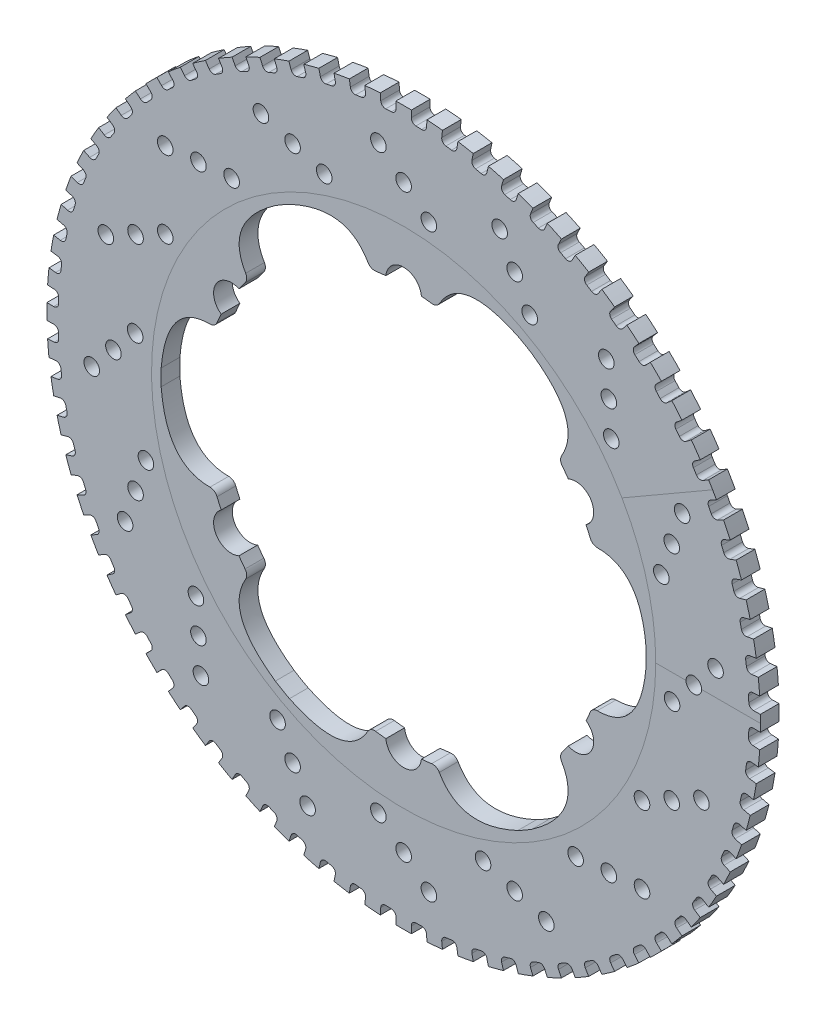
SolidWorks part; units mm, degrees
material "1023 Carbon Steel Sheet (SS)"
ref_plane "Front Plane" through (0, 0, 0) normal (0, 0, 1) x (1, 0, 0)
ref_plane "Top Plane" through (0, 0, 0) normal (0, 1, 0) x (1, 0, 0)
ref_plane "Right Plane" through (0, 0, 0) normal (1, 0, 0) x (0, 0, -1)
sketch "Sketch2" plane through (0, 0, 0) normal (0, 0, 1) x (1, 0, 0)
  circle A0 centre (0, 0) radius 95.25
  circle A1 centre (0, 0) radius 64.77
  circle A2 centre (0, 0) radius 53.086 construction
  dimension "D1" = 190.5
  dimension "D2" = 30.48
  dimension "D3" = 106.172
extrude "RotorSwept" add sketch "Sketch2" along normal blind 5
sketch "Sketch3" plane through (0, 0, 5) normal (0, 0, 1) x (1, 0, 0)
  line L0 (0, 53.086) -> (0, 64.77) construction
  circle A0 centre (0, 0) radius 53.086 construction
  circle A1 centre (0, 53.086) radius 4.7625
  circle A2 centre (0, 0) radius 53.721
  circle A3 centre (0, 0) radius 64.77 construction
  spline S0 degree 2 poles (-8.89, 52.9803) (-14.4253, 64.6738) (-30.48, 57.15) knots 0 0 0 1 1 1
  spline S1 degree 2 poles (8.89, 52.9803) (14.4253, 64.6738) (30.48, 57.15) knots 0 0 0 1 1 1
  circle M3 centre (0, 0) radius 64.77
  dimension "D1" = 106.172
  dimension "D2" = 9.525
  dimension "D5" = 11.43
  dimension "D4" = 8.89
  dimension "D6" = 30.48
  dimension "D7" = 3.81
  dimension "D3" = 0.635
extrude "FloatPinIF" add sketch "Sketch3" along direction (0, 0, 1) on the side against the normal through all contours A2 S1 S0 A1 M3 region at (0, 59.9234, 5)
pattern_circular "FloatPinPattern" count 6 over 360 about axis through (0, 0, 5) along (0, 0, -1) of "FloatPinIF" reverse direction yes
sketch "Sketch4" plane through (0, 0, 5) normal (0, 0, 1) x (1, 0, 0)
  line L0 (-6.7401, 83.2668) -> (6.7401, 71.6732) construction
  line L1 (0, 0) -> (-6.7401, 83.2668) construction
  line L2 (6.7401, 71.6732) -> (0, 0) construction
  circle A0 centre (0, 0) radius 67.31 construction
  circle A1 centre (0, 0) radius 95.25 construction
  circle A2 centre (0, 0) radius 92.71 construction
  circle A3 centre (0, 0) radius 77.47 construction
  circle A4 centre (0, 77.47) radius 2.0828
  circle A5 centre (-6.7401, 83.2668) radius 2.0828
  circle A6 centre (6.7401, 71.6732) radius 2.0828
  point P13 (0, 77.47)
  dimension "D1" = 27.94
  dimension "D4" = 4.1656
  dimension "D6" = 4.1656
  dimension "D7" = 4.1656
  dimension "D5" = 17.78
  dimension "D8" = 10
  dimension "D2" = 25.4
  dimension "D3" = 10.16
extrude "Holes" cut sketch "Sketch4" against normal through all
pattern_circular "HolesPattern" count 16 over 360 about axis through (0, 0, 5) along (0, 0, -1) of "Holes" reverse direction yes
sketch "Sketch5" plane through (0, 0, 5) normal (0, 0, 1) x (1, 0, 0)
  line L0 (0, 0) -> (0, 95.25) construction
  line L1 (0, 0) -> (-2.0779, 95.2273)
  line L2 (0, 0) -> (2.0779, 95.2273)
  line L3 (0, 0) -> (6.2296, 95.0461)
  line L4 (0, 0) -> (10.3696, 94.6839)
  line L5 (0, 0) -> (14.4898, 94.1414)
  line L6 (0, 0) -> (18.5824, 93.4198)
  line L7 (0, 0) -> (22.6396, 92.5203)
  line L8 (0, 0) -> (26.6537, 91.4447)
  line L9 (0, 0) -> (30.6171, 90.1951)
  line L10 (0, 0) -> (34.5222, 88.7737)
  line L11 (0, 0) -> (38.3616, 87.1834)
  line L12 (0, 0) -> (42.128, 85.4271)
  line L13 (0, 0) -> (45.8142, 83.5082)
  line L14 (0, 0) -> (49.4132, 81.4304)
  line L15 (0, 0) -> (52.9181, 79.1975)
  line L16 (0, 0) -> (56.3222, 76.8138)
  line L17 (0, 0) -> (59.6192, 74.284)
  line L18 (0, 0) -> (62.8027, 71.6127)
  line L19 (0, 0) -> (65.8666, 68.8052)
  line L20 (0, 0) -> (68.8052, 65.8666)
  line L21 (0, 0) -> (71.6127, 62.8027)
  line L22 (0, 0) -> (74.284, 59.6192)
  line L23 (0, 0) -> (76.8138, 56.3222)
  line L24 (0, 0) -> (79.1975, 52.9181)
  line L25 (0, 0) -> (81.4304, 49.4132)
  line L26 (0, 0) -> (83.5082, 45.8142)
  line L27 (0, 0) -> (85.4271, 42.128)
  line L28 (0, 0) -> (87.1834, 38.3616)
  line L29 (0, 0) -> (88.7737, 34.5222)
  line L30 (0, 0) -> (90.1951, 30.6171)
  line L31 (0, 0) -> (91.4447, 26.6537)
  line L32 (0, 0) -> (92.5203, 22.6396)
  line L33 (0, 0) -> (93.4198, 18.5824)
  line L34 (0, 0) -> (94.1414, 14.4898)
  line L35 (0, 0) -> (94.6839, 10.3696)
  line L36 (0, 0) -> (95.0461, 6.2296)
  line L37 (0, 0) -> (95.2273, 2.0779)
  line L38 (0, 0) -> (95.2273, -2.0779)
  line L39 (0, 0) -> (95.0461, -6.2296)
  line L40 (0, 0) -> (94.6839, -10.3696)
  line L41 (0, 0) -> (94.1414, -14.4898)
  line L42 (0, 0) -> (93.4198, -18.5824)
  line L43 (0, 0) -> (92.5203, -22.6396)
  line L44 (0, 0) -> (91.4447, -26.6537)
  line L45 (0, 0) -> (90.1951, -30.6171)
  line L46 (0, 0) -> (88.7737, -34.5222)
  line L47 (0, 0) -> (87.1834, -38.3616)
  line L48 (0, 0) -> (85.4271, -42.128)
  line L49 (0, 0) -> (83.5082, -45.8142)
  line L50 (0, 0) -> (81.4304, -49.4132)
  line L51 (0, 0) -> (79.1975, -52.9181)
  line L52 (0, 0) -> (76.8138, -56.3222)
  line L53 (0, 0) -> (74.284, -59.6192)
  line L54 (0, 0) -> (71.6127, -62.8027)
  line L55 (0, 0) -> (68.8052, -65.8666)
  line L56 (0, 0) -> (65.8666, -68.8052)
  line L57 (0, 0) -> (62.8027, -71.6127)
  line L58 (0, 0) -> (59.6192, -74.284)
  line L59 (0, 0) -> (56.3222, -76.8138)
  line L60 (0, 0) -> (52.9181, -79.1975)
  line L61 (0, 0) -> (49.4132, -81.4304)
  line L62 (0, 0) -> (45.8142, -83.5082)
  line L63 (0, 0) -> (42.128, -85.4271)
  line L64 (0, 0) -> (38.3616, -87.1834)
  line L65 (0, 0) -> (34.5222, -88.7737)
  line L66 (0, 0) -> (30.6171, -90.1951)
  line L67 (0, 0) -> (26.6537, -91.4447)
  line L68 (0, 0) -> (22.6396, -92.5203)
  line L69 (0, 0) -> (18.5824, -93.4198)
  line L70 (0, 0) -> (14.4898, -94.1414)
  line L71 (0, 0) -> (10.3696, -94.6839)
  line L72 (0, 0) -> (6.2296, -95.0461)
  line L73 (0, 0) -> (2.0779, -95.2273)
  line L74 (0, 0) -> (-2.0779, -95.2273)
  line L75 (0, 0) -> (-6.2296, -95.0461)
  line L76 (0, 0) -> (-10.3696, -94.6839)
  line L77 (0, 0) -> (-14.4898, -94.1414)
  line L78 (0, 0) -> (-18.5824, -93.4198)
  line L79 (0, 0) -> (-22.6396, -92.5203)
  line L80 (0, 0) -> (-26.6537, -91.4447)
  line L81 (0, 0) -> (-30.6171, -90.1951)
  line L82 (0, 0) -> (-34.5222, -88.7737)
  line L83 (0, 0) -> (-38.3616, -87.1834)
  line L84 (0, 0) -> (-42.128, -85.4271)
  line L85 (0, 0) -> (-45.8142, -83.5082)
  line L86 (0, 0) -> (-49.4132, -81.4304)
  line L87 (0, 0) -> (-52.9181, -79.1975)
  line L88 (0, 0) -> (-56.3222, -76.8138)
  line L89 (0, 0) -> (-59.6192, -74.284)
  line L90 (0, 0) -> (-62.8027, -71.6127)
  line L91 (0, 0) -> (-65.8666, -68.8052)
  line L92 (0, 0) -> (-68.8052, -65.8666)
  line L93 (0, 0) -> (-71.6127, -62.8027)
  line L94 (0, 0) -> (-74.284, -59.6192)
  line L95 (0, 0) -> (-76.8138, -56.3222)
  line L96 (0, 0) -> (-79.1975, -52.9181)
  line L97 (0, 0) -> (-81.4304, -49.4132)
  line L98 (0, 0) -> (-83.5082, -45.8142)
  line L99 (0, 0) -> (-85.4271, -42.128)
  line L100 (0, 0) -> (-87.1834, -38.3616)
  line L101 (0, 0) -> (-88.7737, -34.5222)
  line L102 (0, 0) -> (-90.1951, -30.6171)
  line L103 (0, 0) -> (-91.4447, -26.6537)
  line L104 (0, 0) -> (-92.5203, -22.6396)
  line L105 (0, 0) -> (-93.4198, -18.5824)
  line L106 (0, 0) -> (-94.1414, -14.4898)
  line L107 (0, 0) -> (-94.6839, -10.3696)
  line L108 (0, 0) -> (-95.0461, -6.2296)
  line L109 (0, 0) -> (-95.2273, -2.0779)
  line L110 (0, 0) -> (-95.2273, 2.0779)
  line L111 (0, 0) -> (-95.0461, 6.2296)
  line L112 (0, 0) -> (-94.6839, 10.3696)
  line L113 (0, 0) -> (-94.1414, 14.4898)
  line L114 (0, 0) -> (-93.4198, 18.5824)
  line L115 (0, 0) -> (-92.5203, 22.6396)
  line L116 (0, 0) -> (-91.4447, 26.6537)
  line L117 (0, 0) -> (-90.1951, 30.6171)
  line L118 (0, 0) -> (-88.7737, 34.5222)
  line L119 (0, 0) -> (-87.1834, 38.3616)
  line L120 (0, 0) -> (-85.4271, 42.128)
  line L121 (0, 0) -> (-83.5082, 45.8142)
  line L122 (0, 0) -> (-81.4304, 49.4132)
  line L123 (0, 0) -> (-79.1975, 52.9181)
  line L124 (0, 0) -> (-76.8138, 56.3222)
  line L125 (0, 0) -> (-74.284, 59.6192)
  line L126 (0, 0) -> (-71.6127, 62.8027)
  line L127 (0, 0) -> (-68.8052, 65.8666)
  line L128 (0, 0) -> (-65.8666, 68.8052)
  line L129 (0, 0) -> (-62.8027, 71.6127)
  line L130 (0, 0) -> (-59.6192, 74.284)
  line L131 (0, 0) -> (-56.3222, 76.8138)
  line L132 (0, 0) -> (-52.9181, 79.1975)
  line L133 (0, 0) -> (-49.4132, 81.4304)
  line L134 (0, 0) -> (-45.8142, 83.5082)
  line L135 (0, 0) -> (-42.128, 85.4271)
  line L136 (0, 0) -> (-38.3616, 87.1834)
  line L137 (0, 0) -> (-34.5222, 88.7737)
  line L138 (0, 0) -> (-30.6171, 90.1951)
  line L139 (0, 0) -> (-26.6537, 91.4447)
  line L140 (0, 0) -> (-22.6396, 92.5203)
  line L141 (0, 0) -> (-18.5824, 93.4198)
  line L142 (0, 0) -> (-14.4898, 94.1414)
  line L143 (0, 0) -> (-10.3696, 94.6839)
  line L144 (0, 0) -> (-6.2296, 95.0461)
  circle A0 centre (0, 0) radius 92.202
  circle A1 centre (0, 0) radius 95.25 construction
  arc A2 (2.0389, 93.4411) -> (3.2636, 92.1442) centre (3.3086, 93.4134) ccw
  arc A3 (6.1128, 93.2633) -> (4.7797, 92.078) centre (4.8455, 93.3463) cw
  circle A4 centre (0, 0) radius 95.25
  point P16 (0, 0)
  point P154 (0, 0)
  dimension "D1" = 184.404
  dimension "D4" = 1.27
  dimension "D5" = 1.27
  dimension "D2" = 1.25
  dimension "D3" = 72
extrude "ToothCutOut" cut sketch "Sketch5" against normal through all contours L3 A4 L2 A2 A0 A3 region at (4.0915, 93.71, 5)
pattern_circular "ToothCutOutPattern" count 72 over 360 about axis through (0, 0, 5) along (0, 0, -1) of "ToothCutOut" reverse direction yes
sketch "Sketch6" plane through (0, 0, 5) normal (0, 0, 1) x (1, 0, 0)
  line L0 (-95.25, 0) -> (67.31, 0) construction
  line L1 (0, 0) -> (58.2922, 33.655) construction
  line L2 (58.2922, 33.655) -> (82.4889, 47.625)
  line L3 (67.31, 0) -> (95.25, 0)
  circle A0 centre (0, 0) radius 67.31
  circle A1 centre (0, 0) radius 95.25
  point P6 (58.2922, 33.655)
  point P9 (67.31, 0)
  dimension "D2" = 27.94
  dimension "D3" = 190.5
  dimension "D1" = 30
split line "SplitLine"
fillet "Fillet1" radius 2.032 12 edges at (-8.89, -52.9803, 2.5) (8.89, -52.9803, 2.5) (41.4373, -34.1891, 2.5) (50.3273, -18.7912, 2.5) (-50.3273, -18.7912, 2.5) (-41.4373, -34.1891, 2.5) (-41.4373, 34.1891, 2.5) (-50.3273, 18.7912, 2.5) (50.3273, 18.7912, 2.5) (41.4373, 34.1891, 2.5) (8.89, 52.9803, 2.5) (-8.89, 52.9803, 2.5)
